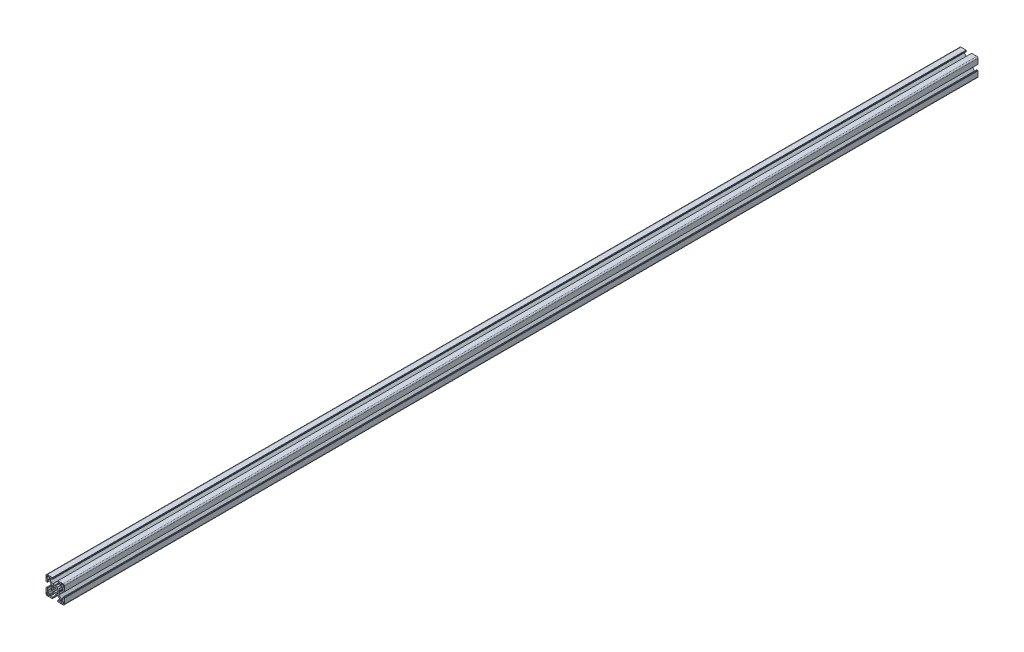
SolidWorks part; units mm, degrees
ref_plane "Front Plane" through (0, 0, 0) normal (0, 0, 1) x (1, 0, 0)
ref_plane "Top Plane" through (0, 0, 0) normal (0, 1, 0) x (1, 0, 0)
ref_plane "Right Plane" through (0, 0, 0) normal (1, 0, 0) x (0, 0, -1)
sketch "Sketch1" plane through (0, 0, 0) normal (0, 0, 1) x (1, 0, 0)
  line L0 (-15, 0) -> (15, 0) construction
  line L1 (0, -15) -> (0, 15) construction
  line L2 (-4.5, 15) -> (4.5, 15) construction
  line L3 (-4, -15) -> (4, -15) construction
  line L4 (-4.5, 15) -> (-4.5, 14.5)
  line L5 (-4.5, 14.5) -> (-4, 14.5)
  line L6 (-4, 14.5) -> (-4, 13.29)
  line L7 (-4.5, 12.79) -> (-7.7675, 12.79)
  line L8 (-8.2675, 12.29) -> (-8.2675, 10.2707)
  line L9 (-8.1211, 9.9171) -> (-4.3504, 6.1464)
  line L10 (-3.9968, 6) -> (0, 6)
  line L11 (0, 0) -> (-15, 15) construction
  line L12 (-4.5, 15) -> (-12.968, 15)
  line L14 (-12.705, 9.5135) -> (-10.5135, 9.5135)
  line L15 (-13.705, 10.5135) -> (-13.705, 12.705)
  line L16 (-12.705, 13.705) -> (-10.5135, 13.705)
  line L17 (-9.5135, 10.5135) -> (-9.5135, 12.705)
  line L18 (-13.705, 9.5135) -> (-9.5135, 13.705) construction
  line L19 (-13.705, 13.705) -> (-9.5135, 9.5135) construction
  line L20 (-3.1568, 4.5038) -> (-1.5303, 3.1477) construction
  line L21 (-4.5038, 3.1568) -> (-3.1477, 1.5303) construction
  line L22 (-6, 3.9968) -> (-6, 0)
  line L23 (-9.9171, 8.1211) -> (-6.1464, 4.3504)
  line L24 (-15, 4.5) -> (-15, 12.968)
  line L25 (-12.29, 8.2675) -> (-10.2707, 8.2675)
  line L26 (-12.79, 4.5) -> (-12.79, 7.7675)
  line L27 (-14.5, 4) -> (-13.29, 4)
  line L28 (-14.5, 4.5) -> (-14.5, 4)
  line L29 (-15, 4.5) -> (-14.5, 4.5)
  circle A0 centre (0, 0) radius 3.5
  arc A1 (-12.968, 15) -> (-15, 12.968) centre (-12.968, 12.968) ccw
  circle A2 centre (0, 0) radius 5.5 construction
  arc A3 (-10.5135, 9.5135) -> (-9.5135, 10.5135) centre (-10.5135, 10.5135) ccw
  arc A4 (-13.705, 12.705) -> (-12.705, 13.705) centre (-12.705, 12.705) cw
  arc A5 (-10.5135, 13.705) -> (-9.5135, 12.705) centre (-10.5135, 12.705) cw
  arc A6 (-12.705, 9.5135) -> (-13.705, 10.5135) centre (-12.705, 10.5135) cw
  arc A7 (-12.79, 4.5) -> (-13.29, 4) centre (-13.29, 4.5) cw
  arc A8 (-12.29, 8.2675) -> (-12.79, 7.7675) centre (-12.29, 7.7675) ccw
  arc A9 (-9.9171, 8.1211) -> (-10.2707, 8.2675) centre (-10.2707, 7.7675) ccw
  arc A10 (-6, 3.9968) -> (-6.1464, 4.3504) centre (-6.5, 3.9968) ccw
  arc A11 (-4.3504, 6.1464) -> (-3.9968, 6) centre (-3.9968, 6.5) ccw
  arc A12 (-4, 13.29) -> (-4.5, 12.79) centre (-4.5, 13.29) cw
  arc A13 (-7.7675, 12.79) -> (-8.2675, 12.29) centre (-7.7675, 12.29) ccw
  arc A14 (-8.2675, 10.2707) -> (-8.1211, 9.9171) centre (-7.7675, 10.2707) ccw
  point P4 (0, 0)
  point P8 (0, 0)
  point P13 (0, 15)
  point P15 (0, -15)
  point P16 (0, 6)
  point P23 (-11.6092, 11.6093)
  point P26 (0, 6)
  point P62 (-12.79, 4)
  point P65 (-12.79, 8.2675)
  point P68 (-10.0636, 8.2675)
  point P71 (-6, 4.2039)
  point P74 (-4.2039, 6)
  point P77 (-4, 12.79)
  point P80 (-8.2675, 12.79)
  point P83 (-8.2675, 10.0636)
  dimension "Center Hole Diameter" = 7
  dimension "D11" = 2.032
  dimension "D9" = 11
  dimension "D13" = 1
  dimension "D14" = 0.5
  dimension "Rail Height" = 30
  dimension "Rail Width" = 30
  dimension "T-Slot Width" = 8
  dimension "T-Slot Depth" = 9
  dimension "D1" = 9
  dimension "D2" = 45
  dimension "D3" = 8
  dimension "D4" = 2.21
  dimension "D5" = 16.535
  dimension "D7" = 2.54
  dimension "D6" = 1.295
  dimension "D8" = 1.246
  dimension "D10" = 10.36
  dimension "D12" = 1.905
sketch "Sketch2" plane through (0, 0, 0) normal (1, 0, 0) x (0, 0, -1)
  line L0 (-76.2, 0) -> (76.2, 0) construction
  line L2 (0, -15) -> (0, 15) construction
  line L3 (0, -15) -> (0, 15) construction
  line L4 (-76.2, -15) -> (-76.2, 15) construction
  line L5 (76.2, -15) -> (76.2, 15) construction
  point P0 (-38.7, 0)
  point P3 (0, 0)
  point P4 (38.7, 0)
  point P12 (-76.2, 0)
  point P14 (76.2, 0)
  dimension "Length" = 152.4
  dimension "D1" = 37.5
sketch "Sketch3" plane through (0, 0, 0) normal (0, 0, 1) x (1, 0, 0)
  line L0 (-4.5038, 3.1568) -> (-3.1477, 1.5303)
  line L1 (0, 3.5) -> (0, 5.5)
  line L2 (-5.5, 0) -> (-3.5, 0)
  line L7 (-6, 3.9968) -> (-6, 0) construction
  line L31 (-9.9171, 8.1211) -> (-6.1464, 4.3504) construction
  line L117 (-12.29, 8.2675) -> (-10.2707, 8.2675) construction
  line L118 (-12.79, 4.5) -> (-12.79, 7.7675) construction
  line L157 (-12.705, 9.5135) -> (-10.5135, 9.5135)
  line L158 (-9.5135, 10.5135) -> (-9.5135, 12.705)
  line L163 (-10.5135, 13.705) -> (-12.705, 13.705)
  line L164 (-13.705, 12.705) -> (-13.705, 10.5135)
  line L165 (-12.705, 9.5135) -> (-10.5135, 9.5135)
  line L166 (-9.5135, 10.5135) -> (-9.5135, 12.705)
  line L167 (-10.5135, 13.705) -> (-12.705, 13.705)
  line L168 (-13.705, 12.705) -> (-13.705, 10.5135)
  line L169 (-14.5, 4) -> (-13.29, 4) construction
  line L170 (-14.5, 4.5) -> (-14.5, 4) construction
  line L171 (-15, 4.5) -> (-14.5, 4.5) construction
  line L172 (-15, 4.5) -> (-15, 12.968) construction
  line L173 (-4.5, 15) -> (-12.968, 15) construction
  line L174 (-4.5, 15) -> (-4.5, 14.5) construction
  line L175 (-4.5, 14.5) -> (-4, 14.5) construction
  line L176 (-4, 14.5) -> (-4, 13.29) construction
  line L177 (-4.5, 12.79) -> (-7.7675, 12.79) construction
  line L178 (-8.2675, 12.29) -> (-8.2675, 10.2707) construction
  line L179 (-8.1211, 9.9171) -> (-4.3504, 6.1464) construction
  line L180 (-3.9968, 6) -> (0, 6) construction
  line L181 (-6, 3.9968) -> (-6, 0.866)
  line L182 (-9.9171, 8.1211) -> (-6.1464, 4.3504)
  line L183 (-12.29, 8.2675) -> (-10.2707, 8.2675)
  line L184 (-12.79, 4.5) -> (-12.79, 7.7675)
  line L185 (-14.5, 4) -> (-13.29, 4)
  line L186 (-14.5, 4.5) -> (-14.5, 4)
  line L187 (-15, 4.5) -> (-14.5, 4.5)
  line L188 (-15, 4.5) -> (-15, 12.968)
  line L189 (-4.5, 15) -> (-12.968, 15)
  line L190 (-4.5, 15) -> (-4.5, 14.5)
  line L191 (-4.5, 14.5) -> (-4, 14.5)
  line L192 (-4, 14.5) -> (-4, 13.29)
  line L193 (-4.5, 12.79) -> (-7.7675, 12.79)
  line L194 (-8.2675, 12.29) -> (-8.2675, 10.2707)
  line L195 (-8.1211, 9.9171) -> (-4.3504, 6.1464)
  line L196 (-3.9968, 6) -> (-0.866, 6)
  line L197 (-0.866, 6) -> (0, 5.5)
  line L198 (0, -15) -> (0, 15) construction
  line L199 (0, 0) -> (-15, 15) construction
  line L200 (0, 0) -> (-15, 15) construction
  line L201 (-3.1568, 4.5038) -> (-1.5303, 3.1477) construction
  line L202 (-3.1568, 4.5038) -> (-1.5303, 3.1477)
  line L203 (-6, 0.866) -> (-5.5, 0)
  line L204 (-15, 0) -> (15, 0) construction
  line L205 (-15, 0) -> (15, 0) construction
  line L206 (0, -15) -> (0, 15) construction
  arc A0 (-3.5, 0) -> (-3.1477, 1.5303) centre (0, 0) cw
  arc A10 (-6, 3.9968) -> (-6.1464, 4.3504) centre (-6.5, 3.9968) ccw construction
  circle A16 centre (0, 0) radius 3.5
  arc A18 (0, 3.5) -> (-1.5303, 3.1477) centre (0, 0) ccw
  arc A20 (-9.9171, 8.1211) -> (-10.2707, 8.2675) centre (-10.2707, 7.7675) ccw construction
  arc A22 (-12.29, 8.2675) -> (-12.79, 7.7675) centre (-12.29, 7.7675) ccw construction
  arc A28 (-13.29, 4) -> (-12.79, 4.5) centre (-13.29, 4.5) ccw construction
  arc A29 (-10.5135, 9.5135) -> (-9.5135, 10.5135) centre (-10.5135, 10.5135) ccw
  arc A30 (-9.5135, 12.705) -> (-10.5135, 13.705) centre (-10.5135, 12.705) ccw
  arc A31 (-12.705, 13.705) -> (-13.705, 12.705) centre (-12.705, 12.705) ccw
  arc A32 (-13.705, 10.5135) -> (-12.705, 9.5135) centre (-12.705, 10.5135) ccw
  arc A33 (-10.5135, 9.5135) -> (-9.5135, 10.5135) centre (-10.5135, 10.5135) ccw
  arc A34 (-9.5135, 12.705) -> (-10.5135, 13.705) centre (-10.5135, 12.705) ccw
  arc A35 (-12.705, 13.705) -> (-13.705, 12.705) centre (-12.705, 12.705) ccw
  arc A36 (-13.705, 10.5135) -> (-12.705, 9.5135) centre (-12.705, 10.5135) ccw
  arc A37 (-12.968, 15) -> (-15, 12.968) centre (-12.968, 12.968) ccw construction
  arc A38 (-4.5, 12.79) -> (-4, 13.29) centre (-4.5, 13.29) ccw construction
  arc A39 (-7.7675, 12.79) -> (-8.2675, 12.29) centre (-7.7675, 12.29) ccw construction
  arc A40 (-8.2675, 10.2707) -> (-8.1211, 9.9171) centre (-7.7675, 10.2707) ccw construction
  arc A41 (-4.3504, 6.1464) -> (-3.9968, 6) centre (-3.9968, 6.5) ccw construction
  arc A42 (-6, 3.9968) -> (-6.1464, 4.3504) centre (-6.5, 3.9968) ccw
  arc A43 (-9.9171, 8.1211) -> (-10.2707, 8.2675) centre (-10.2707, 7.7675) ccw
  arc A44 (-12.29, 8.2675) -> (-12.79, 7.7675) centre (-12.29, 7.7675) ccw
  arc A45 (-13.29, 4) -> (-12.79, 4.5) centre (-13.29, 4.5) ccw
  arc A46 (-12.968, 15) -> (-15, 12.968) centre (-12.968, 12.968) ccw
  arc A47 (-4.5, 12.79) -> (-4, 13.29) centre (-4.5, 13.29) ccw
  arc A48 (-7.7675, 12.79) -> (-8.2675, 12.29) centre (-7.7675, 12.29) ccw
  arc A49 (-8.2675, 10.2707) -> (-8.1211, 9.9171) centre (-7.7675, 10.2707) ccw
  arc A50 (-4.3504, 6.1464) -> (-3.9968, 6) centre (-3.9968, 6.5) ccw
  circle A51 centre (0, 0) radius 5.5 construction
  arc A52 (-3.1568, 4.5038) -> (-4.5038, 3.1568) centre (0, 0) ccw
  dimension "D3" = 60
  dimension "D4" = 60
  dimension "D1" = 0
  dimension "D2" = 0
extrude "Boss-Extrude1" add sketch "Sketch3" along normal mid plane 1500
pattern_circular "CirPattern1" count 4 over 360 about axis through (0, 0, 76.2) along (0, 0, -1) of "Boss-Extrude1"
ref_plane "Contact Plane1" through (15, 0, 0) normal (1, 0, 0) x (0, 0, -1)
ref_plane "Contact Plane2" through (0, -15, 0) normal (0, 1, 0) x (1, 0, 0)
ref_plane "Contact Plane3" through (-15, 0, 0) normal (1, 0, 0) x (0, 0, -1)
ref_plane "Contact Plane4" through (0, 15, 0) normal (0, 1, 0) x (1, 0, 0)
equation "\"D1@Sketch2\" = \"Rail Height@Sketch1\" * 1.25"
equation "\"D1@Sketch1\"=\"T-Slot Width@Sketch1\"+1mm"
equation "\"D3@Sketch1\"=\"T-Slot Width@Sketch1\""
equation "\"D1@Boss-Extrude1\"=\"length\""
equation "\"length\" = 1500"
